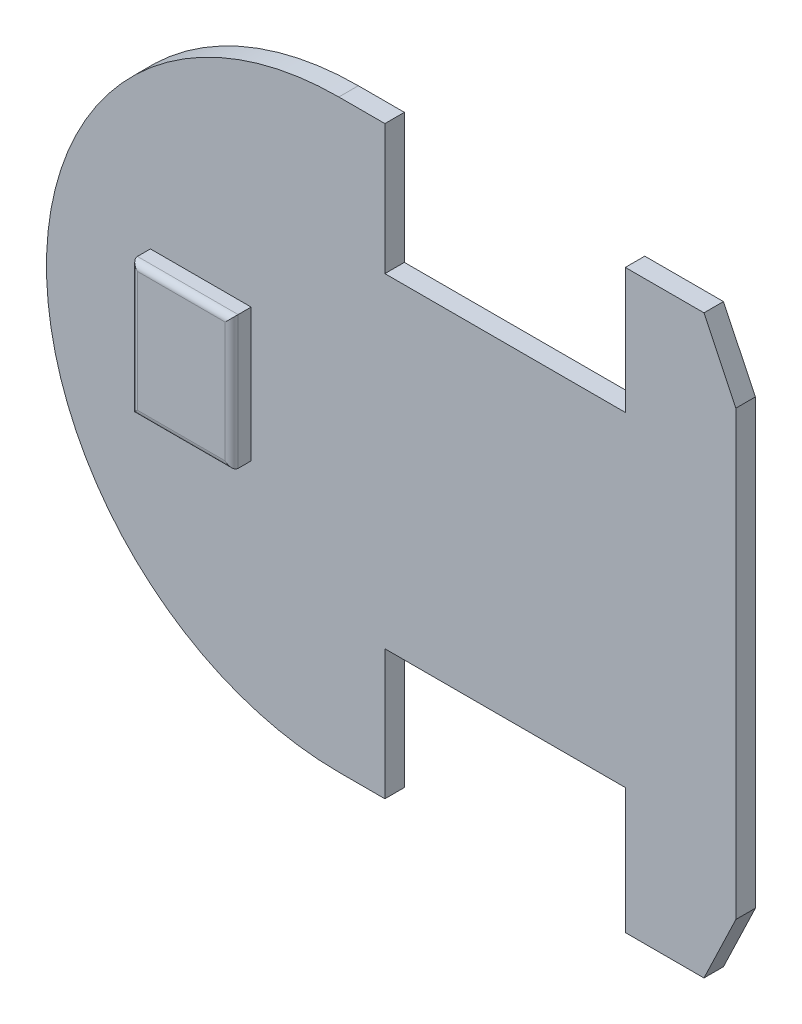
SolidWorks part; units mm, degrees
ref_plane "Front Plane" through (0, 0, 0) normal (1, 0, 0) x (0, 1, 0)
ref_plane "Top Plane" through (0, 0, 0) normal (0, 0, 1) x (0, 1, 0)
ref_plane "Right Plane" through (0, 0, 0) normal (0, 1, 0) x (-1, 0, 0)
sketch "Sketch1" plane through (0, 0, 0) normal (0, 0, 1) x (0, 1, 0)
  line L0 (-45, 0) -> (42.7013, 0) construction
  line L5 (-46.1493, 30.1223) -> (45.7296, -29.8483) construction
  line L6 (-45.2263, -31.0672) -> (43.8507, 30.1223) construction
  line L7 (-1.1493, 75.1223) -> (-1.1493, -29.8777) construction
  line L8 (-46.1493, 23.0351) -> (-26.1493, 23.0351)
  line L10 (-45.4803, -13.9649) -> (-26.1493, -13.9649)
  line L11 (-26.1493, 23.0351) -> (-26.1493, -13.9649)
  line L12 (-45, 0) -> (-26.1493, -13.9649) construction
  line L13 (-45, 0) -> (-26.1493, 23.0351) construction
  line L14 (-46.1493, 30.1223) -> (-46.1493, 23.0351)
  line L15 (-45.4803, -13.9649) -> (-45.4803, -26.0737)
  line L16 (-45.4803, -26.0737) -> (-35.2266, -30.9824)
  line L17 (42.7013, 0) -> (23.8507, 23.0351) construction
  line L18 (42.7013, 0) -> (23.8507, -13.9649) construction
  line L19 (43.1817, -26.0737) -> (32.928, -30.9824)
  line L20 (43.1817, -13.9649) -> (43.1817, -26.0737)
  line L21 (43.8507, 30.1223) -> (43.8507, 23.0351)
  line L22 (23.8507, 23.0351) -> (23.8507, -13.9649)
  line L23 (43.1817, -13.9649) -> (23.8507, -13.9649)
  line L24 (43.8507, 23.0351) -> (23.8507, 23.0351)
  line L25 (-35.2266, -30.9824) -> (32.928, -30.9824)
  line L27 (-11.3993, 59.1223) -> (9.1007, 59.1223)
  line L28 (-11.3993, 59.1223) -> (-11.3993, 43.6223)
  line L29 (-11.3993, 43.6223) -> (9.1007, 43.6223)
  line L30 (9.1007, 59.1223) -> (9.1007, 43.6223)
  line L31 (-11.3993, 59.1223) -> (9.1007, 43.6223) construction
  line L32 (-11.3993, 43.6223) -> (9.1007, 59.1223) construction
  arc A0 (43.8507, 30.1223) -> (-46.1493, 30.1223) centre (-1.1493, 30.1223) ccw
  point P0 (0, 0)
  point P23 (-1.1493, 51.3723)
  dimension "D1" = 90
  dimension "D2" = 60
  dimension "D3" = 37
  dimension "D4" = 20
  dimension "D5" = 15.5
  dimension "D6" = 20.5
  dimension "D7" = 5
  dimension "D8" = 16
  dimension "D9" = 10
  dimension "D10" = 105
extrude "Boss-Extrude1" add sketch "Sketch1" along normal blind 3
extrude "Boss-Extrude3" add sketch "Sketch1<10>" along normal blind 6 contours L29 L30 L27 L28
sketch "Sketch1<10>" plane through (0, 0, 0) normal (0, 0, 1) x (0, 1, 0) same geometry as "Sketch1"
extrude "Cut-Extrude4" cut sketch "Sketch1<12>" along normal blind 3 contours L28 L29 L30 L27
sketch "Sketch1<12>" plane through (0, 0, 0) normal (0, 0, 1) x (0, 1, 0) same geometry as "Sketch1"
fillet "Fillet3" radius 1 4 edges at (-59.1223, -1.1493, 6) (-51.3723, 9.1007, 6) (-43.6223, -1.1493, 6) (-51.3723, -11.3993, 6)
